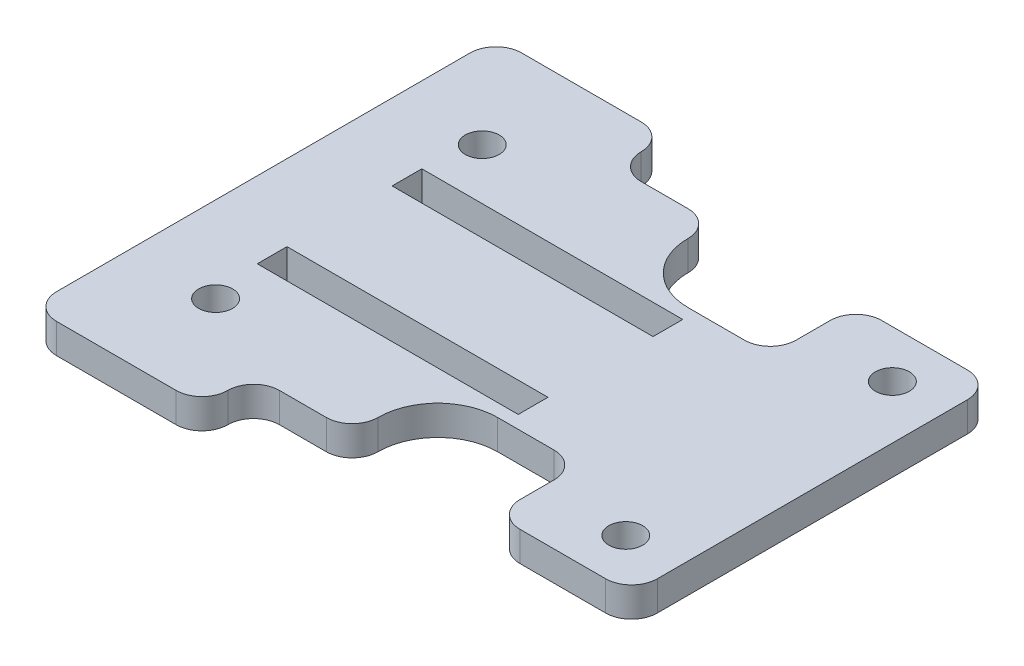
SolidWorks part; units mm, degrees
other "下垫片"
ref_plane "前视基准面" through (0, 0, 0) normal (0, 0, 1) x (1, 0, 0)
ref_plane "上视基准面" through (0, 0, 0) normal (0, 1, 0) x (1, 0, 0)
ref_plane "右视基准面" through (0, 0, 0) normal (1, 0, 0) x (0, 0, -1)
other "Configuration Table"
sketch "草图1" plane through (0, 0, 0) normal (0, 1, 0) x (1, 0, 0)
  line L0 (-89.3251, 0) -> (102.0425, 0) construction
  line L1 (0, 56.7239) -> (0, -62.578) construction
  line L2 (-33.2, -8.1375) -> (7.2, -8.1375)
  line L3 (-33.2, 12.7375) -> (7.2, 12.7375)
  line L4 (-33.2, 12.7375) -> (-33.2, 8.1375)
  line L5 (-33.2, 8.1375) -> (7.2, 8.1375)
  line L6 (7.2, 12.7375) -> (7.2, 8.1375)
  line L7 (-33.2, 12.7375) -> (7.2, 8.1375) construction
  line L8 (-33.2, 8.1375) -> (7.2, 12.7375) construction
  line L9 (7.2, -12.7375) -> (7.2, -8.1375)
  line L10 (-33.2, -12.7375) -> (7.2, -12.7375)
  line L11 (-33.2, -12.7375) -> (-33.2, -8.1375)
  line L14 (-3.25, -26.5375) -> (-3.25, -14.7375)
  line L15 (-3.25, -14.7375) -> (18.75, -14.7375)
  line L16 (18.75, -26.5375) -> (18.75, -14.7375)
  line L17 (-3.25, -26.5375) -> (18.75, -14.7375) construction
  line L18 (-3.25, -14.7375) -> (18.75, -26.5375) construction
  line L19 (-3.25, 14.7375) -> (18.75, 14.7375)
  line L20 (18.75, 26.5375) -> (18.75, 14.7375)
  line L22 (-3.25, 26.5375) -> (-3.25, 14.7375)
  line L23 (-3.25, 29.8695) -> (18.75, 29.8695)
  line L25 (-3.25, -26.5375) -> (-3.25, -29.8695)
  line L26 (-3.25, -29.8695) -> (18.75, -29.8695)
  line L27 (18.75, -26.5375) -> (18.75, -29.8695)
  line L28 (18.75, 26.5375) -> (18.75, 29.8695)
  line L30 (-3.25, 26.5375) -> (-3.25, 29.8695)
  circle A0 centre (-31.75, 20.6375) radius 2.625
  circle A4 centre (31.75, 20.6375) radius 2.625
  circle A5 centre (31.75, -20.6375) radius 2.625
  circle A6 centre (-31.75, -20.6375) radius 2.625
  point P13 (-13, 10.4375)
  point P22 (7.75, -20.6375)
  point P35 (-13, 10.4375)
  dimension "D5" = 5.25
  dimension "D11" = 5.25
  dimension "D1" = 40.4
  dimension "D2" = 31.75
  dimension "D3" = 4.6
  dimension "D4" = 20.6375
  dimension "D6" = 11.8
  dimension "D7" = 22
  dimension "D8" = 11.8
  dimension "D9" = 0
  dimension "D10" = 13
  dimension "D12" = 4.6
  dimension "D13" = 40.4
  dimension "D14" = 13
  dimension "D15" = 10.4375
  dimension "D16" = 2
sketch "草图3" plane through (0, 0, 0) normal (0, 1, 0) x (1, 0, 0)
  line L0 (-55, 0) -> (55, 0) construction
  line L1 (-18.5, -28) -> (40, -28)
  line L3 (-18.5, 28) -> (40, 28)
  line L4 (40, -28) -> (40, 28)
  line L5 (-40, -28) -> (40, 28) construction
  line L6 (-40, 28) -> (40, -28) construction
  line L10 (-45, 28) -> (-45, -28)
  line L12 (-45, -28) -> (-45, -36)
  line L13 (-45, -36) -> (-18.5, -36)
  line L14 (-18.5, -28) -> (-18.5, -36)
  line L15 (-18.5, 28) -> (-18.5, 36)
  line L16 (-45, 36) -> (-18.5, 36)
  line L17 (-45, 28) -> (-45, 36)
  point P0 (0, 0)
  dimension "D1" = 56
  dimension "D2" = 80
  dimension "D3" = 5
  dimension "D4" = 26.5
  dimension "D5" = 8
extrude "凸台-拉伸1" add sketch "草图3" along normal blind 4.6
extrude "切除-拉伸1" cut sketch "草图1" along normal up to surface (4.6 mm away) up to face at (-10.5, 4.6, 0)
fillet "圆角2" radius 4 14 edges at (-3.25, 2.3, -28) (18.75, 2.3, -28) (40, 2.3, -28) (40, 2.3, 28) (18.75, 2.3, 28) (-3.25, 2.3, 28) (18.75, 2.3, -14.7375) (18.75, 2.3, 14.7375) (-18.5, 2.3, 28) (-18.5, 2.3, 36) (-45, 2.3, 36) (-45, 2.3, -36) (-18.5, 2.3, -36) (-18.5, 2.3, -28)
fillet "圆角3" radius 9.2625 2 edges at (-3.25, 2.3, -14.7375) (-3.25, 2.3, 14.7375)
